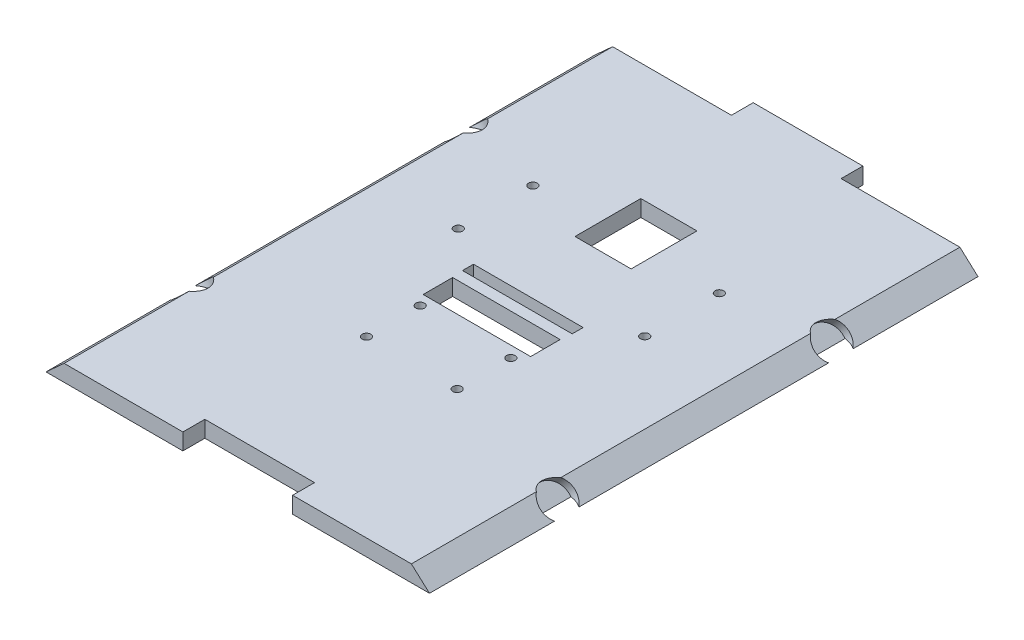
SolidWorks part; units mm, degrees
ref_plane "Front Plane" through (0, 0, 0) normal (0, 0, 1) x (1, 0, 0)
ref_plane "Top Plane" through (0, 0, 0) normal (0, 1, 0) x (1, 0, 0)
ref_plane "Right Plane" through (0, 0, 0) normal (1, 0, 0) x (0, 0, -1)
sketch "Sketch1" plane through (0, 0, 0) normal (0, 0, 1) x (1, 0, 0)
  line L0 (0, 0) -> (0, 44.45) construction
  line L1 (-40.2039, 5.9378) -> (40.2039, 5.9378)
  line L2 (-44.399, 2.1278) -> (44.399, 2.1278)
  line L3 (-40.2039, 5.9378) -> (-44.399, 2.1278)
  line L4 (40.2039, 5.9378) -> (44.399, 2.1278)
  arc A0 (44.399, 2.1278) -> (-44.399, 2.1278) centre (0, 0) ccw construction
  arc A1 (40.2039, 5.9378) -> (-40.2039, 5.9378) centre (0, 0) ccw construction
  dimension "D1" = 88.9
  dimension "D2" = 3.81
  dimension "D3" = 3.81
extrude "Boss-Extrude1" add sketch "Sketch1" along normal blind 127
sketch "Sketch3" plane through (0, 2.1278, 0) normal (0, -1, 0) x (1, 0, 0)
  line L0 (0, 127) -> (0, 0) construction
  line L1 (-44.399, 127) -> (44.399, 127) construction
  line L2 (-44.399, 0) -> (44.399, 0) construction
  line L3 (0, 63.5) -> (44.399, 63.5) construction
  line L4 (-12.7, 127) -> (12.7, 127)
  line L5 (-12.7, 127) -> (-12.7, 121.92)
  line L6 (-12.7, 121.92) -> (12.7, 121.92)
  line L7 (12.7, 127) -> (12.7, 121.92)
  line L8 (44.399, 127) -> (44.399, 0) construction
  line L9 (0, 63.5) -> (-44.399, 63.5) construction
  line L10 (-44.399, 127) -> (-44.399, 0) construction
  line L11 (12.7, -5.08) -> (12.7, 0) construction
  line L13 (-12.7, 0) -> (12.7, 0) construction
  line L14 (-12.7, -5.08) -> (-12.7, 0) construction
  line L15 (-12.7, -5.08) -> (12.7, -5.08) construction
  point P10 (12.7, 124.46)
  dimension "D1" = 25.4
  dimension "D2" = 12.7
  dimension "D3" = 5.08
extrude "Cut-Extrude1" cut sketch "Sketch3" against normal through all
sketch "Sketch4" plane through (0, 2.1278, 0) normal (0, -1, 0) x (1, 0, 0)
  line L0 (12.7, -5.0447) -> (12.7, 0.0353)
  line L1 (-12.7, 0.0353) -> (12.7, 0.0353)
  line L2 (-12.7, -5.0447) -> (-12.7, 0.0353)
  line L3 (-12.7, -5.0447) -> (12.7, -5.0447)
  line L4 (0, 121.92) -> (0, 0.0353) construction
  line L5 (-12.7, 121.92) -> (12.7, 121.92) construction
  dimension "D1" = 25.4
  dimension "D2" = 12.7
  dimension "D3" = 5.08
extrude "Boss-Extrude3" add sketch "Sketch4" against normal blind 3.81
sketch "Sketch5" plane through (0, 2.1278, 0) normal (0, -1, 0) x (-1, 0, 0)
  line L0 (0, -121.92) -> (0, 5.0447) construction
  line L1 (12.7, -121.92) -> (-12.7, -121.92) construction
  line L2 (12.7, 5.0447) -> (-12.7, 5.0447) construction
  line L3 (0, -88.6813) -> (0, -64.8053) construction
  line L4 (12.446, -88.6813) -> (-12.446, -88.6813) construction
  line L5 (12.446, -88.6813) -> (12.446, -64.8053) construction
  line L6 (12.446, -64.8053) -> (-12.446, -64.8053) construction
  line L7 (-12.446, -88.6813) -> (-12.446, -64.8053) construction
  line L8 (23.114, -55.88) -> (-23.114, -55.88) construction
  line L9 (23.114, -55.88) -> (23.114, -35.56) construction
  line L10 (23.114, -35.56) -> (-23.114, -35.56) construction
  line L11 (-23.114, -55.88) -> (-23.114, -35.56) construction
  line L12 (0, -55.88) -> (0, -35.56) construction
  line L13 (-23.114, -45.72) -> (23.114, -45.72) construction
  line L14 (12.446, -76.7433) -> (-12.446, -76.7433) construction
  line L15 (-95.9311, -70.6497) -> (-70.9311, -70.6497) construction
  line L16 (-95.9311, -70.6497) -> (-95.9311, -94.6497) construction
  line L17 (-95.9311, -94.6497) -> (-70.9311, -94.6497) construction
  line L18 (-70.9311, -70.6497) -> (-70.9311, -94.6497) construction
  line L19 (-73.5448, 8.1415) -> (-73.5448, -11.8585) construction
  line L20 (-96.4048, 8.1415) -> (-50.6848, 8.1415) construction
  line L21 (-96.4048, 8.1415) -> (-96.4048, -11.8585) construction
  line L22 (-96.4048, -11.8585) -> (-50.6848, -11.8585) construction
  line L23 (-50.6848, 8.1415) -> (-50.6848, -11.8585) construction
  line L24 (-96.4048, -1.8585) -> (-50.6848, -1.8585) construction
  line L25 (0, -27.178) -> (0, -42.418) construction
  line L26 (6.5, -27.178) -> (-6.5, -27.178)
  line L27 (6.5, -27.178) -> (6.5, -42.418)
  line L28 (6.5, -42.418) -> (-6.5, -42.418)
  line L29 (-6.5, -27.178) -> (-6.5, -42.418)
  line L30 (-12.7, 0) -> (-44.399, 0) construction
  line L31 (0, -62.2653) -> (0, -59.7253) construction
  line L32 (12.7, -62.2653) -> (-12.7, -62.2653)
  line L33 (12.7, -62.2653) -> (12.7, -59.7253)
  line L34 (12.7, -59.7253) -> (-12.7, -59.7253)
  line L35 (-12.7, -62.2653) -> (-12.7, -59.7253)
  line L36 (0, -71.6278) -> (0, -64.8053) construction
  line L37 (12.446, -71.6278) -> (-12.446, -71.6278)
  line L38 (12.446, -71.6278) -> (12.446, -64.8053)
  line L39 (12.446, -64.8053) -> (-12.446, -64.8053)
  line L40 (-12.446, -71.6278) -> (-12.446, -64.8053)
  circle A0 centre (21.59, -54.356) radius 1
  circle A1 centre (21.59, -37.084) radius 1
  circle A2 centre (-21.59, -37.084) radius 1
  circle A3 centre (-21.59, -54.356) radius 1
  circle A4 centre (-10.4422, -74.2033) radius 1
  circle A5 centre (-10.4422, -86.6493) radius 1
  circle A6 centre (10.5578, -74.2033) radius 1
  circle A7 centre (10.5578, -86.6493) radius 1
  circle A8 centre (-93.9311, -72.6497) radius 1
  circle A9 centre (-93.9311, -85.1497) radius 1
  circle A10 centre (-72.9311, -72.6497) radius 1
  circle A11 centre (-72.9311, -85.1497) radius 1
  circle A12 centre (-93.9048, 5.6415) radius 1
  circle A13 centre (-53.1848, 5.6415) radius 1
  circle A14 centre (-53.1848, -9.3585) radius 1
  circle A15 centre (-93.9048, -9.3585) radius 1
  point P53 (0, -34.798)
  dimension "D5" = 15.24
  dimension "D8" = 25.4
  dimension "D9" = 1.524
  dimension "D14" = 9.398
  dimension "D20" = 2
  dimension "D21" = 25
  dimension "D23" = 2
  dimension "D34" = 2
  dimension "D1" = 24.892
  dimension "D2" = 23.876
  dimension "D3" = 0
  dimension "D4" = 0
  dimension "D6" = 24.892
  dimension "D7" = 0
  dimension "D12" = 46.228
  dimension "D13" = 20.32
  dimension "D15" = 9.398
  dimension "D16" = 2.032
  dimension "D17" = 2.032
  dimension "D18" = 21
  dimension "D19" = 21
  dimension "D22" = 24
  dimension "D24" = 21
  dimension "D25" = 12.5
  dimension "D26" = 9.5
  dimension "D27" = 2
  dimension "D28" = 2
  dimension "D29" = 2
  dimension "D30" = 12.446
  dimension "D31" = 2.0038
  dimension "D32" = 20
  dimension "D33" = 45.72
  dimension "D35" = 2.5
  dimension "D36" = 2.5
  dimension "D37" = 13
  dimension "D38" = 6.858
  dimension "D39" = 0
  dimension "D40" = 69.85
  dimension "D41" = 35.56
  dimension "D42" = 0
  dimension "D43" = 2.54
  dimension "D44" = 2.54
  dimension "D45" = 1.524
extrude "Cut-Extrude2" cut sketch "Sketch5" against normal through all
sketch "Sketch6" plane through (-21.1272, 23.263, 0) normal (-0.6723, 0.7403, 0) x (0.7403, 0.6723, 0)
  line L0 (-28.6033, 0) -> (-28.6033, -127.0183) construction
  line L1 (-25.7698, 0) -> (-31.4368, 0) construction
  line L2 (-25.7698, -63.5) -> (-32.513, -63.5) construction
  line L3 (-25.7698, -127) -> (-25.7698, 0) construction
  circle A0 centre (-28.6033, -31.7592) radius 4
  circle A1 centre (-28.6033, -95.2408) radius 4
  point P10 (-28.6033, -63.5092)
  dimension "D1" = 8
  dimension "D2" = 31.75
extrude "Cut-Extrude3" cut sketch "Sketch6" against normal blind 2
sketch "Sketch7" plane through (21.1272, 23.263, 0) normal (0.6723, 0.7403, 0) x (0.7403, -0.6723, 0)
  line L0 (28.6033, -127) -> (28.6033, 0.0251) construction
  line L1 (31.4368, -127) -> (25.7698, -127) construction
  line L2 (25.7698, -63.5) -> (31.6985, -63.5) construction
  line L3 (25.7698, -127) -> (25.7698, 0) construction
  circle A0 centre (28.6033, -95.2374) radius 4
  circle A1 centre (28.6033, -31.7626) radius 4
  point P11 (28.6033, -63.4874)
  dimension "D1" = 8
  dimension "D2" = 31.75
extrude "Cut-Extrude4" cut sketch "Sketch7" against normal blind 2
